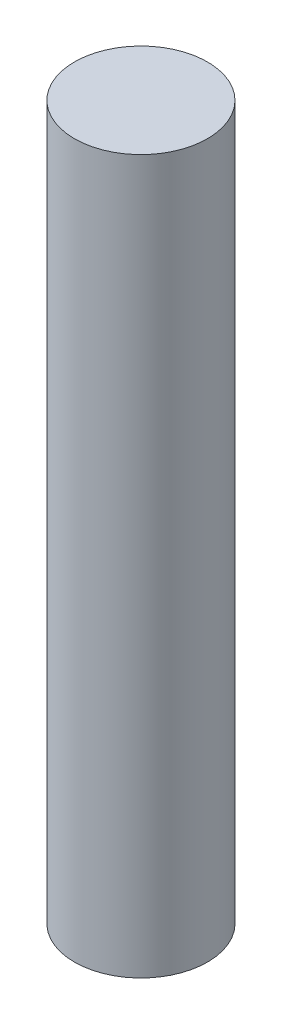
SolidWorks part; units mm, degrees
ref_plane "Front Plane" through (0, 0, 0) normal (0, 0, 1) x (1, 0, 0)
ref_plane "Top Plane" through (0, 0, 0) normal (0, 1, 0) x (1, 0, 0)
ref_plane "Right Plane" through (0, 0, 0) normal (1, 0, 0) x (0, 0, -1)
sketch "Sketch1" plane through (0, 0, 0) normal (0, 1, 0) x (1, 0, 0)
  circle A0 centre (0, 0) radius 3.175
  dimension "D1" = 6.35
extrude "Boss-Extrude1" add sketch "Sketch1" along normal blind 34.036
